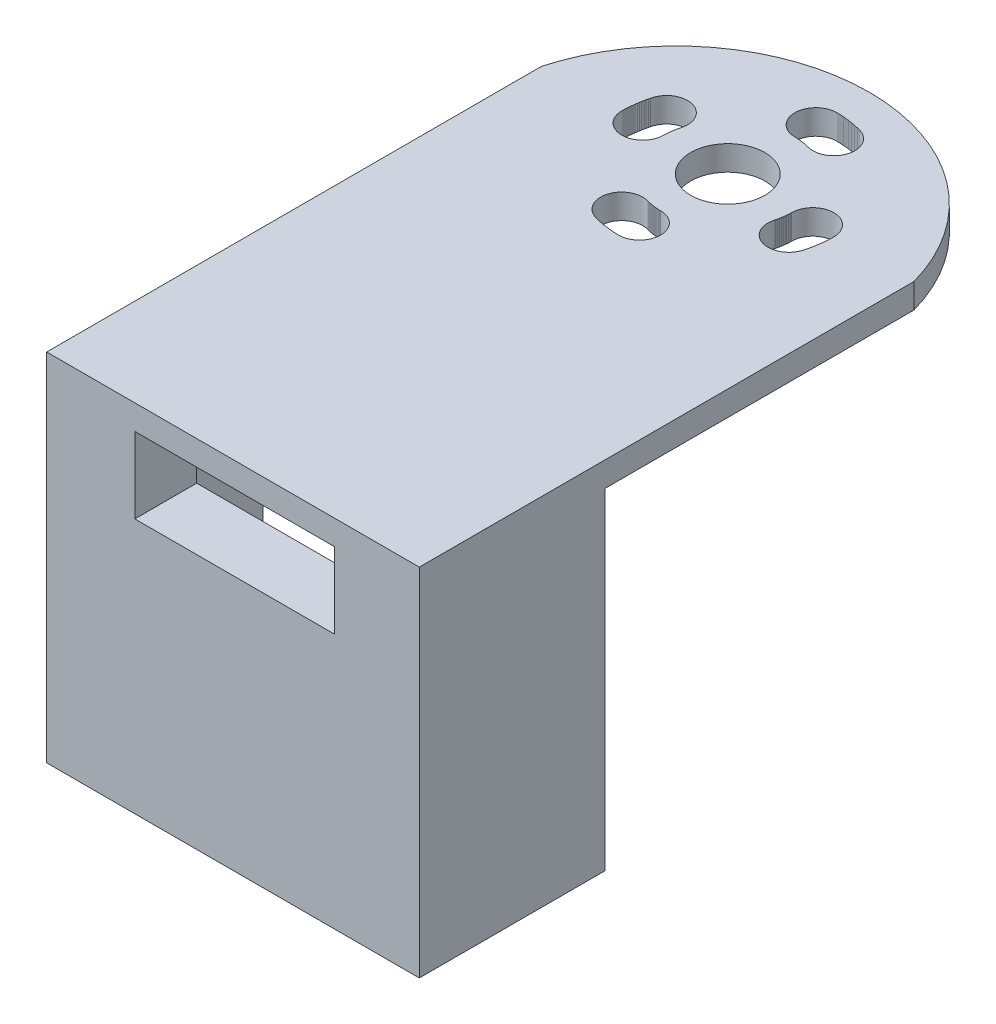
SolidWorks part; units mm, degrees
ref_plane "Front Plane" through (0, 0, 0) normal (0, 0, 1) x (1, 0, 0)
ref_plane "Top Plane" through (0, 0, 0) normal (0, 1, 0) x (1, 0, 0)
ref_plane "Right Plane" through (0, 0, 0) normal (1, 0, 0) x (0, 0, -1)
sketch "Sketch2" plane through (0, 0, 0) normal (0, 1, 0) x (1, 0, 0)
  line L0 (15.061, 0) -> (15.061, 32)
  line L1 (-12.561, 2.5) -> (12.561, 2.5)
  line L2 (-12.561, 2.5) -> (-12.561, 32)
  line L4 (12.561, 2.5) -> (12.561, 32)
  line L5 (15.061, 32) -> (12.561, 32)
  line L7 (-15.061, 32) -> (-15.061, 0)
  line L8 (-15.061, 0) -> (15.061, 0)
  line L10 (-15.061, 32) -> (-12.561, 32)
  point P4 (0, 2.5)
  point P12 (0, 0)
  dimension "D1" = 2.5
  dimension "D2" = 2.5
  dimension "D3" = 29.5
  dimension "D4" = 25.122
extrude "Boss-Extrude1" add sketch "Sketch2" along normal blind 32.5
sketch "Sketch4" plane through (0, 0, 0) normal (0, -1, 0) x (1, 0, 0)
  line L10 (-7.561, -6) -> (-7.561, 0)
  line L13 (-12.561, -2.5) -> (-12.561, -32) construction
  line L18 (-12.561, -10) -> (-7.561, -6)
  line L23 (12.561, -32) -> (12.561, -2.5) construction
  line L26 (12.561, -10) -> (7.561, -6)
  line L33 (-15.061, -32) -> (-15.061, 0) construction
  line L36 (15.061, 0) -> (15.061, -32) construction
  line L38 (-7.561, 0) -> (-15.061, 0)
  line L39 (7.561, -6) -> (7.561, 0)
  line L40 (7.561, 0) -> (15.061, 0)
  line L41 (-15.061, 0) -> (-15.061, -32)
  line L42 (-15.061, -32) -> (-12.561, -32)
  line L43 (-12.561, -32) -> (-15.061, -32) construction
  line L44 (-12.561, -32) -> (-12.561, -10)
  line L45 (12.561, -10) -> (12.561, -32)
  line L46 (12.561, -32) -> (15.061, -32)
  line L47 (15.061, -32) -> (15.061, 0)
  circle A2 centre (-10.2499, -4.95) radius 1.05
  circle A5 centre (10.2499, -4.95) radius 1.05
  dimension "D4" = 6
  dimension "D5" = 2.1
  dimension "D1" = 7.5
  dimension "D2" = 7.5
  dimension "D3" = 10
extrude "Boss-Extrude2" add sketch "Sketch4" along normal blind 2.5
sketch "Sketch5" plane through (0, 32.5, 0) normal (0, 1, 0) x (1, 0, 0)
  line L0 (-15.061, 32) -> (-10.2499, 32)
  line L9 (-10.2499, 32) -> (-6.25, 26)
  line L13 (-15.061, 0) -> (15.061, 0) construction
  line L14 (15.061, 0) -> (-15.061, 0)
  line L15 (-15.061, 0) -> (-15.061, 32)
  line L20 (15.061, 0) -> (15.061, 32)
  line L21 (-6.25, 26) -> (6.25, 26)
  line L22 (6.25, 26) -> (10.2499, 32)
  line L23 (10.2499, 32) -> (15.061, 32)
  circle A0 centre (-10.2499, 4.95) radius 1.05 construction
  circle A1 centre (-10.2499, 8.7) radius 1.05
  circle A2 centre (10.2499, 8.7) radius 1.05
  point P6 (0, 26)
  dimension "D4" = 0
  dimension "D1" = 8.7
  dimension "D2" = 12.5
  dimension "D3" = 20.4998
  dimension "D5" = 6
extrude "Boss-Extrude3" add sketch "Sketch5" along normal blind 3
sketch "Sketch6" plane through (-15.061, 0, 0) normal (-1, 0, 0) x (0, 0, 1)
  line L1 (-32, -2.5) -> (-32, 29.6998)
  line L5 (-32, 35.5) -> (-32, -2.5) construction
  line L7 (0, 35.5) -> (0, -2.5) construction
  line L8 (-12.5, -2.5) -> (-12.5, 35.5)
  line L9 (-32, 35.5) -> (0, 35.5) construction
  line L10 (-12.5, 35.5) -> (-32, 35.5)
  line L11 (-32, 35.5) -> (-32, 29.6998)
  line L12 (0, -2.5) -> (-32, -2.5) construction
  line L13 (-32, -2.5) -> (-12.5, -2.5)
  dimension "D2" = 12.5
extrude "Cut-Extrude1" cut sketch "Sketch6" against normal through all
ref_plane "Plane1" through (0, 16.5, 0) normal (0, -1, 0) x (-1, 0, 0)
sketch "Sketch13" plane through (0, 0, 0) normal (0, 0, 1) x (1, 0, 0)
  line L1 (-15.061, 35.5) -> (15.061, 35.5)
  line L2 (-15.061, 35.5) -> (-15.061, -2.5)
  line L3 (-15.061, -2.5) -> (15.061, -2.5)
  line L4 (15.061, 35.5) -> (15.061, -2.5)
extrude "Boss-Extrude7" add sketch "Sketch13" along normal blind 2.5
sketch "Sketch14" plane through (0, 0, 2.5) normal (0, 0, 1) x (1, 0, 0)
  line L0 (15.061, 35.5) -> (-15.061, 35.5) construction
  line L1 (-7.9361, 35.5) -> (8.206, 35.5)
  line L2 (-7.9361, 35.5) -> (-7.9361, 29.3758)
  line L3 (-7.9361, 29.3758) -> (8.206, 29.3758)
  line L4 (8.206, 35.5) -> (8.206, 29.3758)
extrude "Cut-Extrude2" cut sketch "Sketch14" against normal through all both and the other way through all
sketch "Sketch15" plane through (0, 0, -12.5) normal (0, 0, -1) x (-1, 0, 0)
  line L0 (15.061, -2.5) -> (15.061, 35.5) construction
  line L1 (-15.061, 35.5) -> (15.061, 35.5)
  line L2 (-15.061, 35.5) -> (-15.061, 37.5)
  line L3 (-15.061, 37.5) -> (15.061, 37.5)
  line L4 (15.061, 35.5) -> (15.061, 37.5)
  dimension "D1" = 2
extrude "Boss-Extrude8" add sketch "Sketch15" against normal up to surface (15 mm away) and the other way blind 40 up to face at (0.0675, 24.469, 2.5)
sketch "Sketch16" plane through (0, 37.5, 0) normal (0, 1, 0) x (1, 0, 0)
  line L0 (-15.061, -2.5) -> (15.061, -2.5) construction
  circle A0 centre (0, 37.5) radius 3
  dimension "D1" = 6
  dimension "D2" = 40
extrude "Cut-Extrude3" cut sketch "Sketch16" against normal through all both and the other way through all
sketch "Sketch17" plane through (0, 37.5, 0) normal (0, 1, 0) x (1, 0, 0)
  circle A0 centre (1.8162, 44.2603) radius 1.7
  circle A2 centre (0, 37.5) radius 3 construction
  dimension "D1" = 3.4
  dimension "D2" = 1.8162
  dimension "D3" = 6.7603
extrude "Cut-Extrude4" cut sketch "Sketch17" against normal through all both and the other way through all
ref_axis "Axis1" through (0, 35.5, -37.5) along (0, 1, 0)
pattern_circular "CirPattern1" count 15 every 1 about axis through (0, 35.5, -37.5) along (0, 1, 0) of "Cut-Extrude4"
pattern_circular "CirPattern2" count 4 over 360 about axis through (0, 35.5, -37.5) along (0, 1, 0) of "CirPattern1"
sketch "Sketch19" plane through (0, 0, -12.5) normal (0, 0, -1) x (-1, 0, 0)
  line L1 (-15.061, 8.7299) -> (15.061, 8.7299)
  line L2 (-15.061, 8.7299) -> (-15.061, -7.1783)
  line L3 (-15.061, -7.1783) -> (15.061, -7.1783)
  line L4 (15.061, 8.7299) -> (15.061, -7.1783)
extrude "Cut-Extrude5" cut sketch "Sketch19" against normal through all both and the other way through all
sketch "Sketch23" plane through (0, 37.5, 0) normal (0, 1, 0) x (1, 0, 0)
  line L9 (-15.061, 52.5) -> (-15.061, -2.5) construction
  line L10 (15.061, 52.5) -> (15.061, -2.5) construction
  line L11 (-15.061, 37.5) -> (-15.061, 55.7627)
  line L12 (-15.061, 55.7627) -> (15.061, 55.1353)
  line L13 (15.061, 55.1353) -> (15.061, 37.5)
  arc A1 (-15.061, 37.5) -> (15.061, 37.5) centre (0, 33.3084) cw
extrude "Cut-Extrude8" cut sketch "Sketch23" against normal through all both and the other way through all
